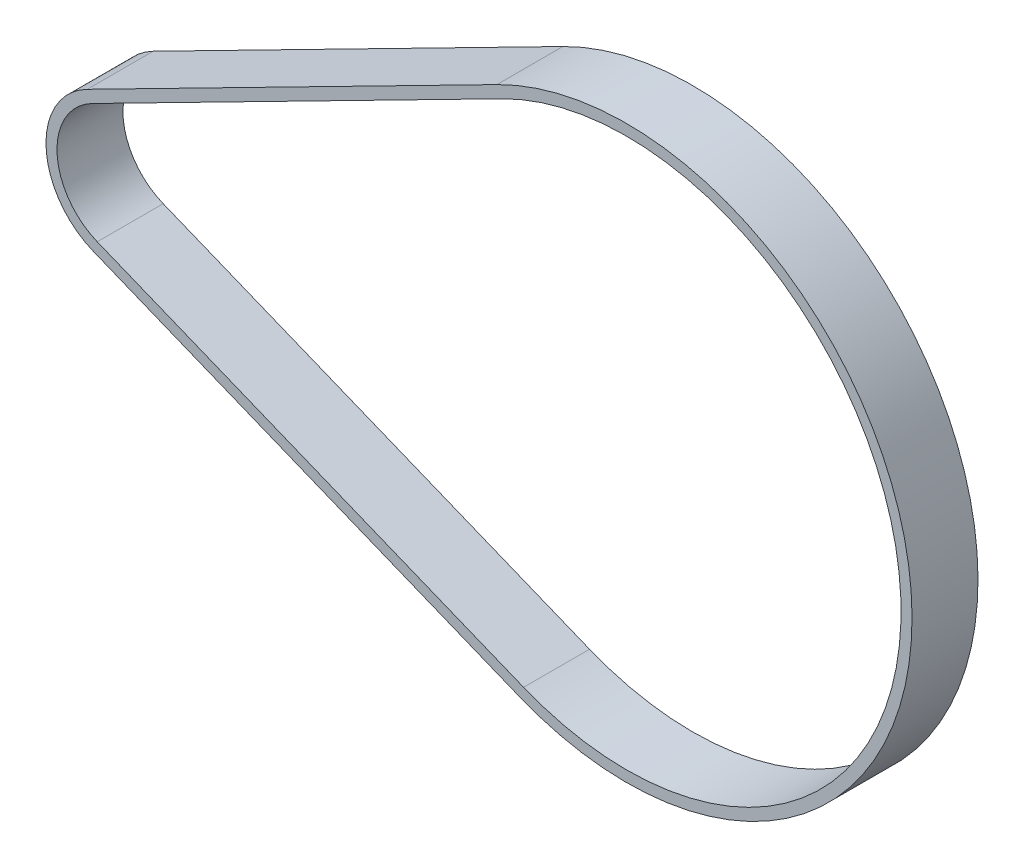
SolidWorks part; units mm, degrees
ref_plane "Front Plane" through (0, 0, 0) normal (0, 0, 1) x (1, 0, 0)
ref_plane "Top Plane" through (0, 0, 0) normal (0, 1, 0) x (1, 0, 0)
ref_plane "Right Plane" through (0, 0, 0) normal (1, 0, 0) x (0, 0, -1)
sketch "Sketch2" plane through (0, 0, 0) normal (0, 0, 1) x (1, 0, 0)
  line L0 (0, 0) -> (1, 0) construction
  line L1 (0, 0) -> (0, 1) construction
  line L4 (36.4325, -24.1072) -> (-2.3496, -8.3987)
  line L5 (-2.8518, 3.171) -> (34.4235, 22.1805)
  arc A1 (34.4235, 22.1805) -> (36.4325, -24.1072) centre (45.9925, -0.5048) cw
  arc A2 (-2.3496, -8.3987) -> (-2.8518, 3.171) centre (0.0399, -2.4993) cw
extrude "Extrude-Thin1" add sketch "Sketch2" against normal blind 6 from offset 1 thin offset against normal yes thin type mid plane wall 1
